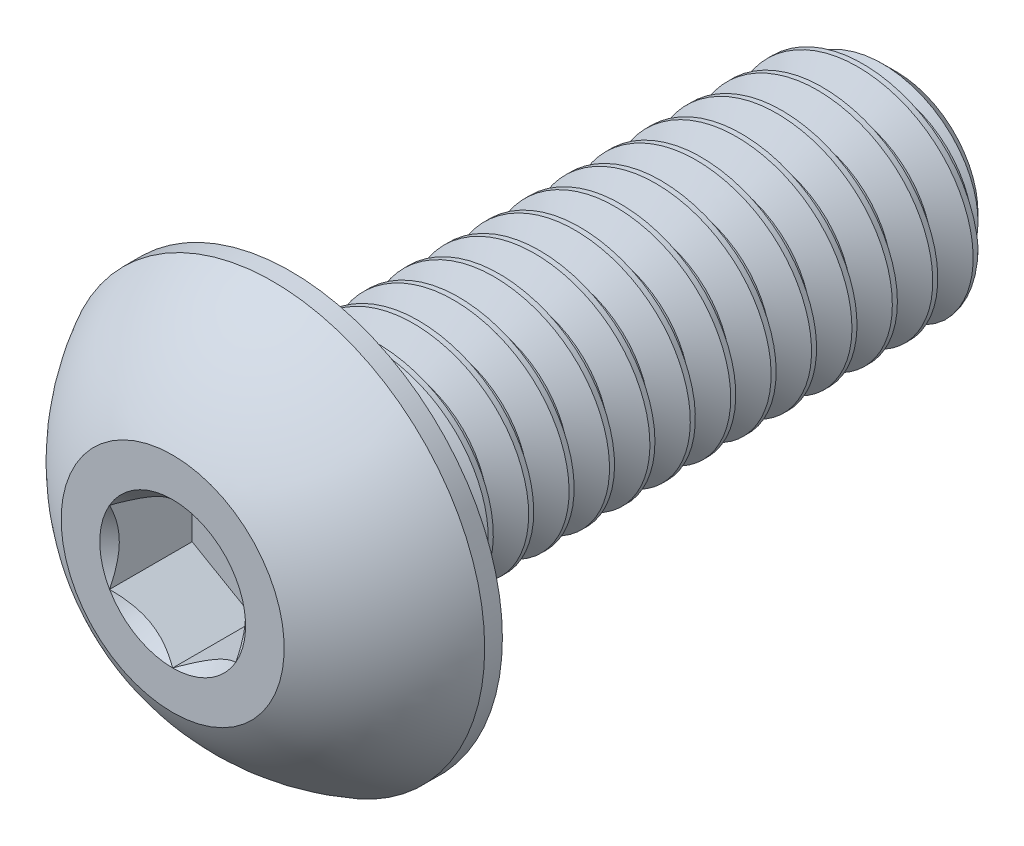
SolidWorks part; units mm, degrees
ref_plane "Front" through (0, 0, 0) normal (0, 0, 1) x (1, 0, 0)
ref_plane "Top" through (0, 0, 0) normal (0, 1, 0) x (1, 0, 0)
ref_plane "Right" through (0, 0, 0) normal (1, 0, 0) x (0, 0, -1)
sketch "Sketch1" plane through (0, 0, 0) normal (1, 0, 0) x (0, 0, -1)
  line L2 (1.8542, 1.7526) -> (11.3792, 1.7526)
  line L3 (11.3792, 1.7526) -> (11.3792, 0)
  line L4 (11.3792, 0) -> (1.8542, 0)
  line L6 (1.5761, 3.3274) -> (1.8542, 3.3274) construction
  line L7 (11.3792, 1.7526) -> (11.3792, -1.7526) construction
  line L8 (0, 0) -> (1.8542, 0) construction
  line L9 (1.8542, 3.3274) -> (1.8542, -3.3274) construction
  line L11 (1.8542, 1.7526) -> (1.8542, 0)
  line L13 (0, 0.9922) -> (0, -0.9922) construction
  line L14 (0, 0.9922) -> (0, 1.7526) construction
  arc A3 (0, 1.7526) -> (1.5761, 3.3274) centre (3.326, 0) cw construction
  dimension "D1" = 0.2781
  dimension "Head Ht" = 1.8542
  dimension "Head Dia" = 6.6548
  dimension "Dia" = 3.5052
  dimension "Lg" = 9.525
  dimension "Hex" = 1.9844
revolve "Revolve1" add sketch "Sketch1" angle 360 about L4
sketch "Sketch3" plane through (0, 0, -11.3792) normal (0, 0, -1) x (-1, 0, 0)
  circle A0 centre (0, 0) radius 1.7526
curve "Helix/Spiral1" pitch 0.635 height 10.16 radius 1.7526 centre (0, 0, -11.3792) axis (0, 0, 1) start towards (0, 1, 0)
sketch "Sketch2" plane through (0, 0, 0) normal (1, 0, 0) x (0, 0, -1)
  line L0 (11.3792, 1.7526) -> (11.9348, 1.7526)
  line L1 (11.9348, 1.7526) -> (11.6967, 1.3402)
  line L2 (11.6967, 1.3402) -> (11.6173, 1.3402)
  line L3 (11.6173, 1.3402) -> (11.3792, 1.7526)
  line L4 (11.4983, 1.5464) -> (11.8158, 1.5464) construction
  dimension "D1" = 60
  dimension "D2" = 0.0794
  dimension "D3" = 0.3175
chamfer "Chamfer1" distance 0.4763 angle 45 1 edges at (0, 1.7526, -11.3792)
sweep "Cut-Sweep1" cut profiles "Sketch2" path "Helix/Spiral1"
sketch "Sketch7" plane through (0, 0, 0) normal (1, 0, 0) x (0, 0, -1)
  line L6 (1.5761, 3.3274) -> (1.8542, 3.3274) construction
  line L8 (0, 0) -> (1.8542, 0) construction
  line L11 (1.8542, 3.3274) -> (1.8542, -3.3274) construction
  line L12 (1.5761, 3.3274) -> (1.8542, 3.3274)
  line L13 (0, 0) -> (1.8542, 0)
  line L14 (0, 0.9922) -> (0, -0.9922) construction
  line L15 (1.8542, 3.3274) -> (1.8542, 0)
  line L16 (0, 1.7526) -> (0, 0)
  arc A2 (1.5761, 3.3274) -> (0, 1.7526) centre (3.326, 0) ccw construction
  arc A3 (1.5761, 3.3274) -> (0, 1.7526) centre (3.326, 0) ccw
revolve "Revolve2" add sketch "Sketch7" angle 360 about L13
sketch "Sketch5" plane through (0, 0, 0) normal (0, 0, 1) x (1, 0, 0)
  line L1 (0.9922, -0.5728) -> (0.9922, 0.5728)
  line L2 (0.9922, 0.5728) -> (0, 1.1457)
  line L3 (0, 1.1457) -> (-0.9922, 0.5728)
  line L4 (-0.9922, 0.5728) -> (-0.9922, -0.5728)
  line L5 (-0.9922, -0.5728) -> (0, -1.1457)
  line L6 (0, -1.1457) -> (0.9922, -0.5728)
  circle A0 centre (0, 0) radius 0.9922 construction
extrude "Cut-Extrude2" cut sketch "Sketch5" against normal blind 1.2979
sketch "Sketch6" plane through (0, 0, 0) normal (0, 0, 1) x (1, 0, 0)
  circle A0 centre (0, 0) radius 1.1457
extrude "Cut-Extrude3" cut sketch "Sketch6" against normal blind 1.2979 draft 45
sketch "Sketch9" [suppressed] plane through (0, 0, -1.4986) normal (0, 0, 1) x (1, 0, 0)
  circle A2 centre (0, 0) radius 1.4224
extrude "Boss-Extrude2" [suppressed] add sketch "Sketch9" against normal offset from surface (12.7 mm away) 31.75 up to face at (0, 1.2763, -11.3792)
sketch "Sketch10" plane through (0, 0, 0) normal (1, 0, 0) x (0, 0, -1)
  line L0 (11.3792, 1.7526) -> (11.3792, -1.7526) construction
  point P0 (10.4267, -1.7526)
  dimension "D1" = 0.9525
equation "\"D3@Helix/Spiral1\" = \"Lg@Sketch1\" + \"D4@Helix/Spiral1\""
equation "\"D2@Sketch2\" = \"D4@Helix/Spiral1\" * .125"
equation "\"D3@Sketch2\" = \"D4@Helix/Spiral1\" * .5"
equation "\"D1@Chamfer1\" = \"D4@Helix/Spiral1\" * .75"
equation "\"D1@Cut-Extrude2\" = \"Head Ht@Sketch1\" * .7"
equation "\"D1@Sketch1\" = \"Head Ht@Sketch1\" * .15"
equation "\"D1@Sketch10\" = \"D4@Helix/Spiral1\" * 1.5"
equation "\"D1@Cut-Extrude3\" = \"D1@Cut-Extrude2\""
